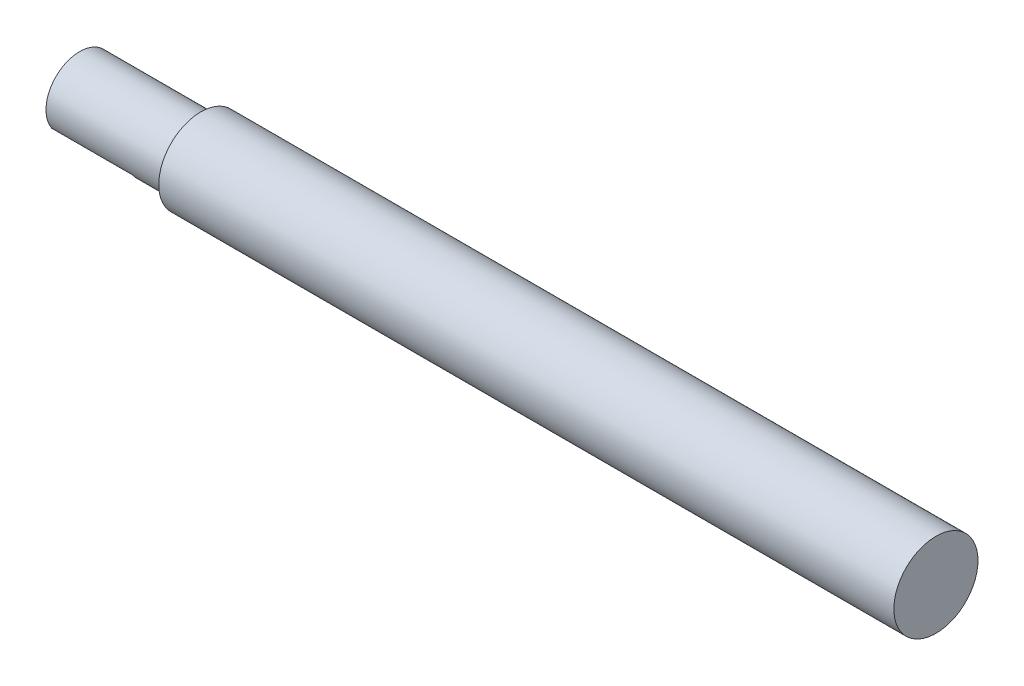
SolidWorks part; units mm, degrees
material "2024-T4"
ref_plane "Front Plane" through (0, 0, 0) normal (0, 0, 1) x (1, 0, 0)
ref_plane "Top Plane" through (0, 0, 0) normal (0, 1, 0) x (1, 0, 0)
ref_plane "Right Plane" through (0, 0, 0) normal (1, 0, 0) x (0, 0, -1)
sketch "Sketch2" plane through (0, 0, 0) normal (1, 0, 0) x (0, 0, -1)
  circle A0 centre (0, 0) radius 3.9688
  dimension "D1" = 7.9375
extrude "Boss-Extrude1" add sketch "Sketch2" along normal blind 69.342
sketch "Sketch3" plane through (0, 0, 0) normal (1, 0, 0) x (0, 0, -1)
  circle A0 centre (0, 0) radius 3.175
  dimension "D1" = 6.35
extrude "Boss-Extrude2" add sketch "Sketch3" against normal blind 11.43
sketch "Sketch4" plane through (-11.43, 0, 0) normal (-1, 0, 0) x (0, 0, 1)
  line L0 (0, 0) -> (-2.6305, -1.778) construction
  line L1 (-2.6305, -1.778) -> (2.6305, -1.778)
  line L2 (2.6305, -1.778) -> (0, 0) construction
  line L3 (0, -1.778) -> (0, 0) construction
  line L4 (-2.6305, -1.778) -> (-4.0993, -3.461)
  line L5 (-4.0993, -3.461) -> (1.3959, -3.6523)
  line L6 (1.3959, -3.6523) -> (3.0284, -2.6195)
  line L7 (3.0284, -2.6195) -> (2.6305, -1.778)
  circle A0 centre (0, 0) radius 3.175 construction
  dimension "D1" = 1.778
extrude "Cut-Extrude1" cut sketch "Sketch4" against normal blind 7.62
